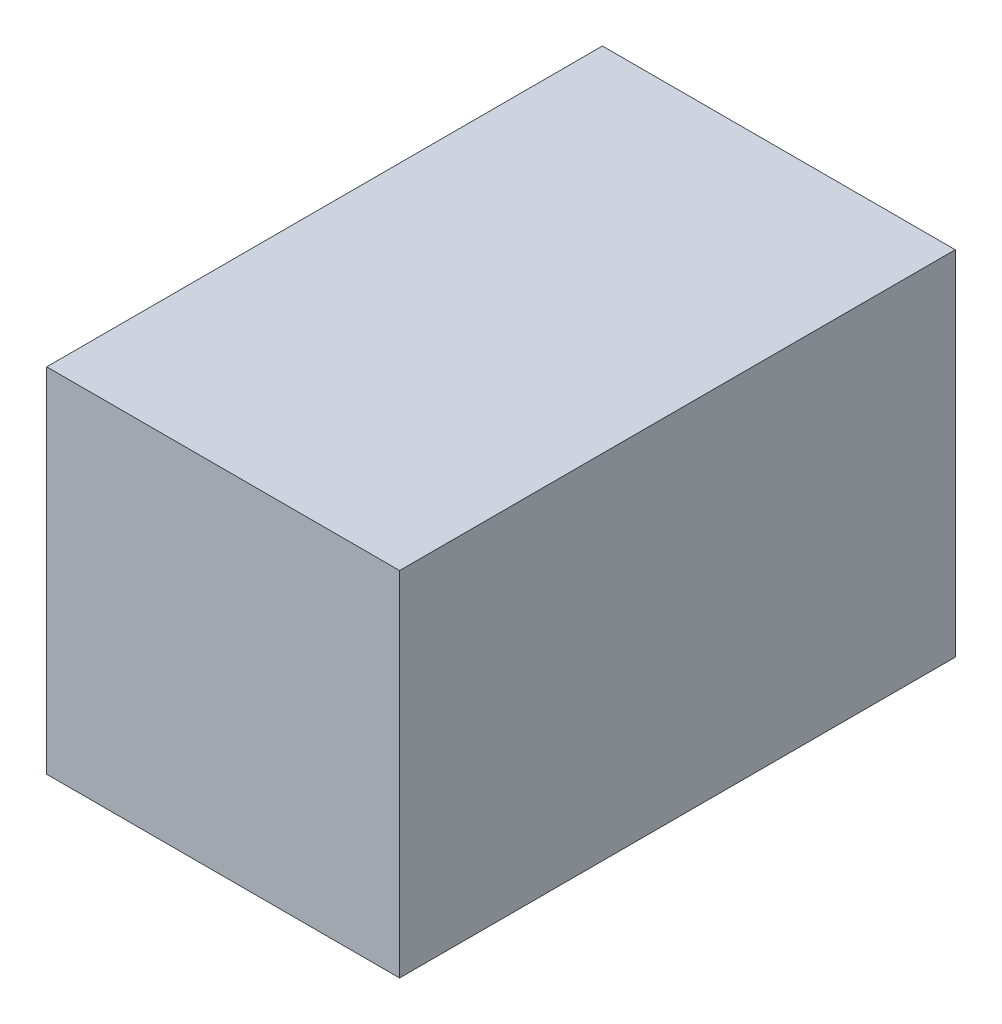
SolidWorks part; units mm, degrees
ref_plane "Front Plane" through (0, 0, 0) normal (0, 0, 1) x (1, 0, 0)
ref_plane "Top Plane" through (0, 0, 0) normal (0, 1, 0) x (1, 0, 0)
ref_plane "Right Plane" through (0, 0, 0) normal (1, 0, 0) x (0, 0, -1)
sketch "Sketch1" plane through (0, 0, 0) normal (0, 0, 1) x (1, 0, 0)
  line L1 (-22.225, 22.225) -> (22.225, 22.225)
  line L2 (-22.225, 22.225) -> (-22.225, -22.225)
  line L3 (-22.225, -22.225) -> (22.225, -22.225)
  line L4 (22.225, 22.225) -> (22.225, -22.225)
  line L5 (-22.225, 22.225) -> (22.225, -22.225) construction
  line L6 (-22.225, -22.225) -> (22.225, 22.225) construction
  point P0 (0, 0)
  dimension "D1" = 44.45
  dimension "D2" = 44.45
extrude "Boss-Extrude1" add sketch "Sketch1" along normal blind 35 and the other way blind 35
